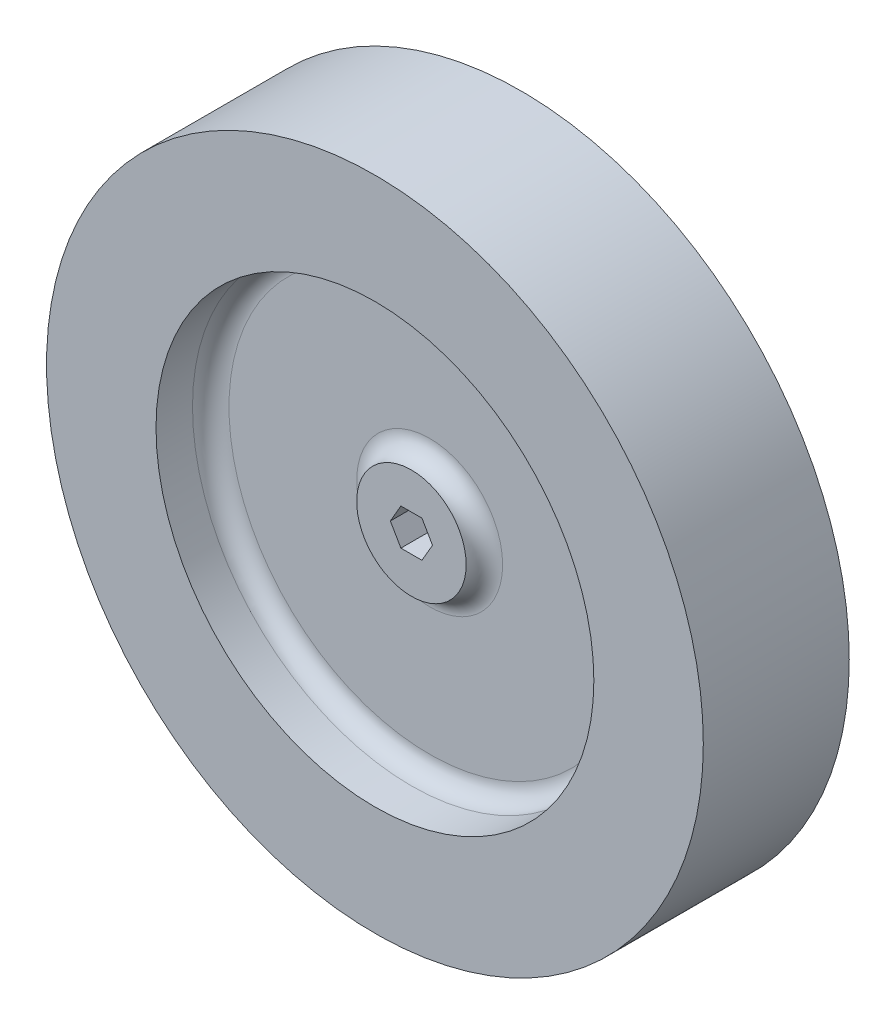
SolidWorks part; units mm, degrees
material "AISI 1020 Steel, Cold Rolled"
ref_plane "Front Plane" through (0, 0, 0) normal (0, 0, 1) x (1, 0, 0)
ref_plane "Top Plane" through (0, 0, 0) normal (0, 1, 0) x (1, 0, 0)
ref_plane "Right Plane" through (0, 0, 0) normal (1, 0, 0) x (0, 0, -1)
sketch "Sketch1" plane through (0, 0, 0) normal (0, 0, 1) x (1, 0, 0)
  line L1 (7.3323, 0) -> (3.6662, 6.35)
  line L2 (3.6662, 6.35) -> (-3.6662, 6.35)
  line L3 (-3.6662, 6.35) -> (-7.3323, 0)
  line L4 (-7.3323, 0) -> (-3.6662, -6.35)
  line L5 (-3.6662, -6.35) -> (3.6662, -6.35)
  line L6 (3.6662, -6.35) -> (7.3323, 0)
  circle A0 centre (0, 0) radius 114.3
  circle A1 centre (0, 0) radius 76.2
  circle A2 centre (0, 0) radius 6.35 construction
  circle A3 centre (0, 0) radius 19.05
  dimension "D1" = 228.6
  dimension "D2" = 152.4
  dimension "D4" = 38.1
  dimension "D3" = 12.7
extrude "Boss-Extrude1" add sketch "Sketch1" along normal blind 25.4 and the other way blind 25.4 contours A0 A1 region at (-111.0671, 0, 0)
extrude "Boss-Extrude2" add sketch "Sketch1<4>" along normal blind 6.35 and the other way blind 6.35 contours A1 A3 region at (-74.0447, 0, 0)
sketch "Sketch1<4>" plane through (0, 0, 0) normal (0, 0, 1) x (1, 0, 0) same geometry as "Sketch1"
extrude "Boss-Extrude3" add sketch "Sketch1<5>" along normal blind 12.7 and the other way blind 12.7 contours A3 L6 L5 L4 L3 L2 L1 region at (-18.5112, 0, 0)
sketch "Sketch1<5>" plane through (0, 0, 0) normal (0, 0, 1) x (1, 0, 0) same geometry as "Sketch1"
fillet "Fillet1" radius 6.35 4 edges at (76.2, 0, -6.35) (19.05, 0, -6.35) (19.05, 0, 6.35) (76.2, 0, 6.35)
ref_axis "Axis1" through (0, 0, -25.4) along (0, 0, 1)
